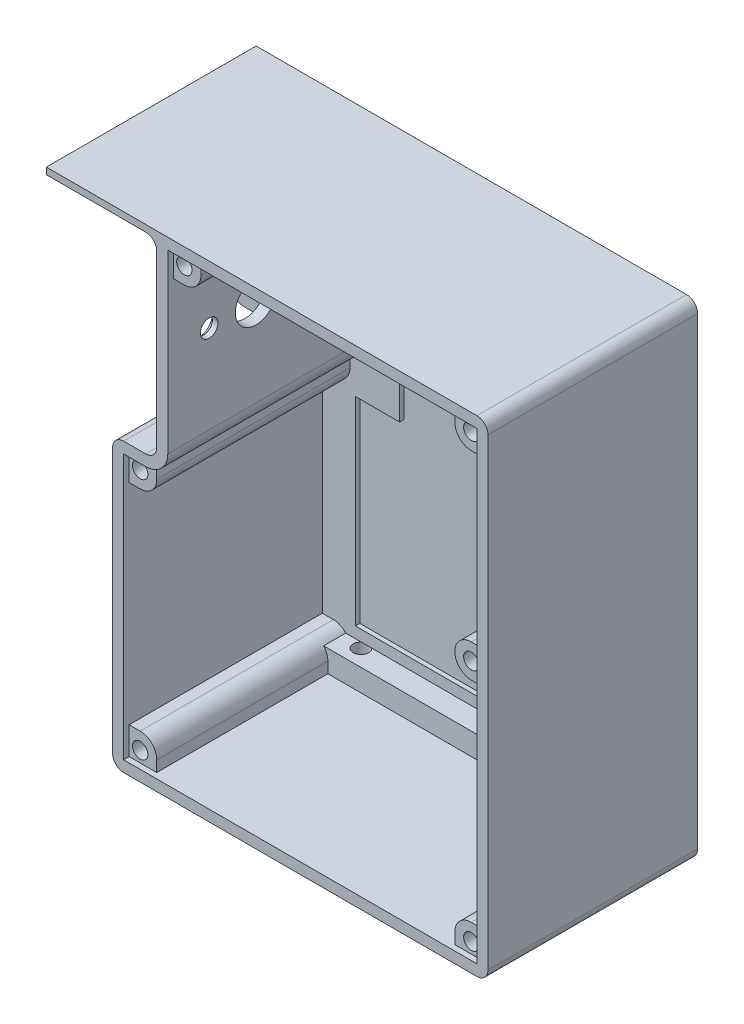
SolidWorks part; units mm, degrees
note: The reader was unsure of these and kept them because the rebuilt part matched: shared geometry of "草图9<3>", "草图2<3>", "草图1<3>", "草图11<2>".
ref_plane "前视基准面" through (0, 0, 0) normal (0, 0, 1) x (1, 0, 0)
ref_plane "上视基准面" through (0, 0, 0) normal (0, 1, 0) x (1, 0, 0)
ref_plane "右视基准面" through (0, 0, 0) normal (1, 0, 0) x (0, 0, -1)
sketch "草图1" plane through (0, 0, 0) normal (0, 0, 1) x (1, 0, 0)
  line L0 (0, 0) -> (68, 0)
  line L1 (68, 0) -> (68, 88)
  line L2 (68, 88) -> (8, 88)
  line L3 (8, 88) -> (8, 52)
  line L4 (8, 52) -> (0, 52)
  line L5 (0, 52) -> (0, 0)
  line L6 (8, 44) -> (8, 8)
  line L7 (8, 8) -> (60, 8)
  line L8 (60, 8) -> (60, 80)
  line L9 (60, 80) -> (16, 80)
  line L10 (16, 80) -> (16, 44)
  line L11 (16, 44) -> (8, 44)
  dimension "D1" = 8
  dimension "D2" = 68
  dimension "D3" = 36
  dimension "D4" = 88
  dimension "D5" = 8
extrude "凸台-拉伸1" add sketch "草图1" along normal blind 38 contours L1 L2 L3 L4 L5 L0
shell "抽壳1" thickness 2
sketch "草图9" plane through (0, 0, 0) normal (0, 0, 1) x (1, 0, 0)
  line L1 (8, 88) -> (-12, 88)
  line L2 (8, 88) -> (8, 52)
  line L3 (8, 52) -> (-12, 52)
  line L4 (-12, 88) -> (-12, 52)
  line L5 (-12, 88) -> (8, 88)
  line L6 (-12, 88) -> (-12, 86.8)
  line L7 (-12, 86.8) -> (8, 86.8)
  line L8 (8, 88) -> (8, 86.8)
  dimension "D1" = 20
  dimension "D2" = 1.2
extrude "凸台-拉伸3" add sketch "草图9" along normal blind 6 contours L7 L4 L3 L2
extrude "凸台-拉伸4" add sketch "草图9<3>" along normal blind 38 contours L4 L7 L2 L1
sketch "草图9<3>" plane through (0, 0, 0) normal (0, 0, 1) x (1, 0, 0) same geometry as "草图9"
fillet "圆角1" radius 2 6 edges at (68, 0, 19) (0, 0, 19) (68, 88, 19) (8, 52, 22) (8, 86.8, 22) (0, 52, 3)
fillet "圆角2" radius 4 2 edges at (10, 50, 20) (-12, 52, 3)
fillet "圆角4" radius 2 1 edges at (0, 52, 22)
sketch "草图3" plane through (0, 0, 2) normal (0, 0, 1) x (1, 0, 0)
  line L0 (66, 88) -> (-12, 88) construction
  line L2 (61, 81) -> (67, 81)
  line L3 (9, 87) -> (15, 87)
  line L4 (9, 87) -> (9, 81)
  line L5 (9, 81) -> (15, 81)
  line L6 (15, 87) -> (15, 81)
  line L7 (9, 87) -> (15, 81) construction
  line L8 (9, 81) -> (15, 87) construction
  line L9 (67, 87) -> (67, 81)
  line L10 (61, 87) -> (61, 81)
  line L11 (61, 87) -> (67, 81) construction
  line L12 (61, 81) -> (67, 87) construction
  line L13 (61, 87) -> (67, 87)
  line L21 (68, 2) -> (68, 86) construction
  line L22 (61, 1) -> (67, 1)
  line L23 (67, 7) -> (67, 1)
  line L24 (61, 7) -> (61, 1)
  line L25 (61, 7) -> (67, 1) construction
  line L26 (61, 1) -> (67, 7) construction
  line L27 (61, 7) -> (67, 7)
  line L28 (1, 45) -> (7, 45)
  line L29 (7, 51) -> (7, 45)
  line L30 (1, 51) -> (1, 45)
  line L31 (1, 51) -> (7, 45) construction
  line L32 (1, 45) -> (7, 51) construction
  line L33 (1, 51) -> (7, 51)
  line L34 (1, 1) -> (7, 1)
  line L35 (7, 7) -> (7, 1)
  line L36 (1, 7) -> (1, 1)
  line L37 (1, 7) -> (7, 1) construction
  line L38 (1, 1) -> (7, 7) construction
  line L39 (1, 7) -> (7, 7)
  line L40 (2, 0) -> (66, 0) construction
  line L41 (0, 50) -> (0, 2) construction
  line L42 (6, 52) -> (2, 52) construction
  line L43 (61, 51) -> (67, 51)
  line L44 (61, 51) -> (67, 45) construction
  line L45 (67, 51) -> (67, 45)
  line L46 (61, 45) -> (67, 45)
  line L47 (61, 45) -> (67, 51) construction
  line L48 (61, 51) -> (61, 45)
  circle A0 centre (12, 84) radius 1.4
  circle A2 centre (64, 84) radius 1.4
  circle A5 centre (64, 4) radius 1.4
  circle A6 centre (4, 48) radius 1.4
  circle A7 centre (4, 4) radius 1.4
  circle A8 centre (64, 48) radius 1.4
  point P46 (0, 0)
  point P47 (0, 0)
  dimension "D1" = 2.8
  dimension "D2" = 6
  dimension "D3" = 4
  dimension "D4" = 6
  dimension "D6" = 4
  dimension "D7" = 4
  dimension "D11" = 4
  dimension "D12" = 4
  dimension "D13" = 4
  dimension "D14" = 4
  dimension "D15" = 4
  dimension "D16" = 4
  dimension "D5" = 6
  dimension "D8" = 6
  dimension "D9" = 6
  dimension "D10" = 6
extrude "凸台-拉伸2" add sketch "草图3" along normal blind 35
fillet "圆角3" radius 3 7 edges at (7, 7, 19.5) (7, 45, 19.5) (61, 7, 19.5) (61, 45, 19.5) (61, 51, 19.5) (61, 81, 19.5) (15, 81, 19.5)
sketch "草图2" plane through (8, 0, 0) normal (-1, 0, 0) x (0, 0, 1)
  line L0 (0, 88) -> (0, 52) construction
  line L1 (38, 84.8) -> (38, 54) construction
  line L2 (38, 88) -> (0, 88) construction
  circle A0 centre (22, 70) radius 3.75
  circle A1 centre (30.5, 70) radius 1.6
  circle A2 centre (13.5, 70) radius 1.6
  circle A3 centre (22, 70) radius 12.5
  dimension "D1" = 7.5
  dimension "D2" = 3.2
  dimension "D3" = 8.5
  dimension "D4" = 8.5
  dimension "D5" = 22
  dimension "D6" = 18
  dimension "D7" = 16
extrude "切除-拉伸1" cut sketch "草图2" against normal blind 30 contours A0 | A1 | A2 | A3
chamfer "倒角1" distance 1 angle 45 2 edges at (8, 68.4, 30.5) (8, 68.4, 13.5)
extrude "切除-拉伸2" cut sketch "草图2<3>" against normal blind 5 from offset 2 contours A3
sketch "草图2<3>" plane through (8, 0, 0) normal (-1, 0, 0) x (0, 0, 1) same geometry as "草图2"
extrude "切除-拉伸4" cut sketch "草图1<3>" along normal blind 10 from offset 1.2 contours L10 L11 L6 L7 L8 L9
sketch "草图1<3>" plane through (0, 0, 0) normal (0, 0, 1) x (1, 0, 0) same geometry as "草图1"
sketch "草图10" plane through (-12, 0, 0) normal (-1, 0, 0) x (0, 0, 1)
  line L0 (38, 88) -> (0, 88) construction
  circle A0 centre (3, 82) radius 1.4
  circle A1 centre (3, 62) radius 1.4
  dimension "D1" = 2.8
  dimension "D4" = 20
  dimension "D2" = 6
extrude "切除-拉伸5" cut sketch "草图10" against normal blind 8
sketch "草图11" plane through (0, 0, 0) normal (0, -1, 0) x (1, 0, 0)
  line L0 (68, 38) -> (68, 0) construction
  line L1 (0, 0) -> (0, 38) construction
  line L2 (2, 0) -> (66, 0) construction
  line L3 (6, 6) -> (62, 6)
  line L4 (6, 6) -> (6, 0)
  line L5 (6, 0) -> (62, 0)
  line L6 (62, 6) -> (62, 0)
  line L7 (6, 6) -> (62, 0) construction
  line L8 (6, 0) -> (62, 6) construction
  circle A0 centre (10, 3) radius 1.4
  circle A1 centre (34, 3) radius 1.4
  circle A2 centre (58, 3) radius 1.4
  point P16 (0, 0)
  dimension "D1" = 2.8
  dimension "D2" = 10
  dimension "D3" = 10
  dimension "D4" = 6
  dimension "D5" = 24
  dimension "D6" = 56
extrude "凸台-拉伸5" add sketch "草图11" against normal blind 6
extrude "切除-拉伸6" cut sketch "草图11<2>" against normal blind 6 contours A0 | A2 | A1
sketch "草图11<2>" plane through (0, 0, 0) normal (0, -1, 0) x (1, 0, 0) same geometry as "草图11"
